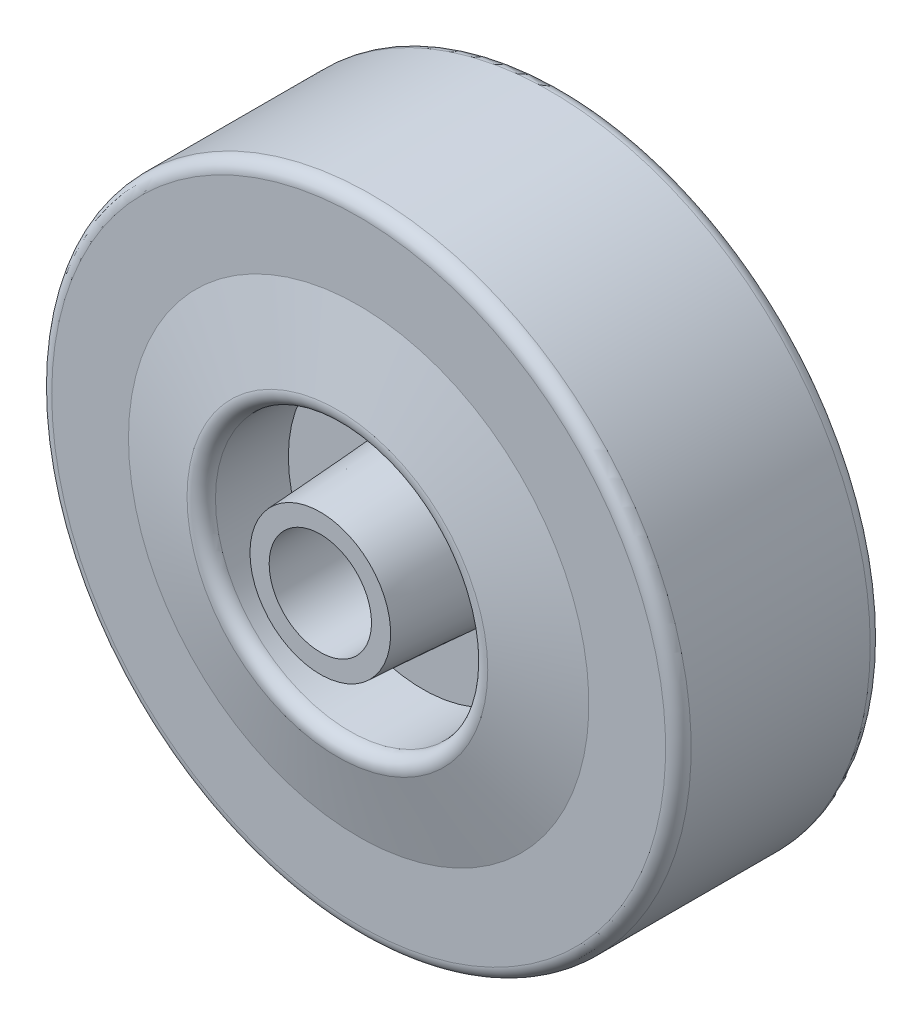
SolidWorks part; units mm, degrees
material "EPDM"
ref_plane "Plan de face" through (0, 0, 0) normal (0, 0, 1) x (1, 0, 0)
ref_plane "Plan de dessus" through (0, 0, 0) normal (0, 1, 0) x (1, 0, 0)
ref_plane "Plan de droite" through (0, 0, 0) normal (1, 0, 0) x (0, 0, -1)
sketch "Esquisse1" plane through (0, 0, 0) normal (0, 1, 0) x (1, 0, 0)
  line L0 (0, 12.6051) -> (0, -10.3469) construction
  line L1 (0, 0) -> (4, 0) construction
  line L2 (4, -11) -> (4, 11)
  line L3 (4, 11) -> (5.5, 11)
  line L4 (5.5, 11) -> (6, 3)
  line L5 (6, 3) -> (10.5, 3)
  line L6 (10.5, 3) -> (10.5, 10)
  line L7 (10.5, 10) -> (18, 8)
  line L8 (18, 8) -> (25, 8)
  line L9 (25, 8) -> (25, -8)
  line L10 (25, 0) -> (4, 0) construction
  line L11 (4, -11) -> (5.5, -11)
  line L12 (5.5, -11) -> (6, -3)
  line L13 (6, -3) -> (10.5, -3)
  line L14 (10.5, -3) -> (10.5, -10)
  line L15 (10.5, -10) -> (18, -8)
  line L16 (18, -8) -> (25, -8)
  point P5 (25, 0)
  dimension "D1" = 4
  dimension "D2" = 25
  dimension "D3" = 1.5
  dimension "D4" = 2
  dimension "D5" = 5
  dimension "D6" = 8
  dimension "D7" = 10
  dimension "D8" = 7.5
  dimension "D9" = 11
  dimension "D10" = 8
revolve "Révolution1" add sketch "Esquisse1" angle 360 about L0
fillet "Congé1" radius 1 2 edges at (-25, 0, 8) (-25, 0, -8)
fillet "Congé2" radius 1 2 edges at (-10.5, 0, -10) (-10.5, 0, 10)
